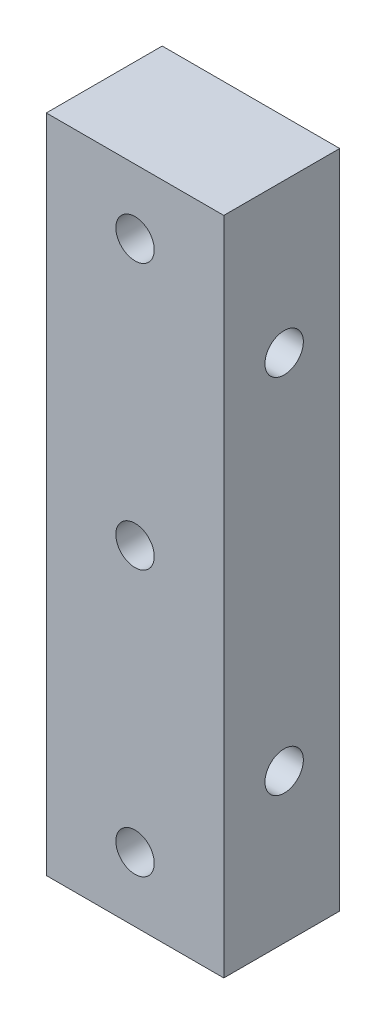
SolidWorks part; units mm, degrees
ref_plane "Front Plane" through (0, 0, 0) normal (0, 0, 1) x (1, 0, 0)
ref_plane "Top Plane" through (0, 0, 0) normal (0, 1, 0) x (1, 0, 0)
ref_plane "Right Plane" through (0, 0, 0) normal (1, 0, 0) x (0, 0, -1)
sketch "Sketch1" plane through (0, 0, 0) normal (0, 0, 1) x (1, 0, 0)
  line L1 (-9.3345, 34.7345) -> (9.3345, 34.7345)
  line L2 (-9.3345, 34.7345) -> (-9.3345, -34.7345)
  line L3 (-9.3345, -34.7345) -> (9.3345, -34.7345)
  line L4 (9.3345, 34.7345) -> (9.3345, -34.7345)
  line L5 (-9.3345, 34.7345) -> (9.3345, -34.7345) construction
  line L6 (-9.3345, -34.7345) -> (9.3345, 34.7345) construction
  point P0 (0, 0)
  dimension "D1" = 18.669
  dimension "D2" = 69.469
extrude "Boss-Extrude1" add sketch "Sketch1" along normal blind 12.192
sketch "Sketch2" plane through (9.3345, 0, 0) normal (1, 0, 0) x (0, 0, -1)
  line L0 (-5.842, 19.05) -> (-5.842, -19.05) construction
  line L1 (-12.192, -34.7345) -> (-12.192, 34.7345) construction
  line L2 (0, -34.7345) -> (0, 34.7345) construction
  point P2 (-5.842, 0)
  point P7 (0, 0)
  dimension "D1" = 6.35
  dimension "D2" = 38.1
hole_wizard "Tap Drill for #10-32 Tap1" positions "Sketch3" profile "Sketch4" hole size "#10-32" standard "ANSI Inch" end condition through all
sketch "Sketch3" plane through (9.3345, 0, 0) normal (1, 0, 0) x (0, 0, -1)
  point P0 (-5.842, 19.05)
  point P3 (-5.842, -19.05)
sketch "Sketch4" plane through (9.3345, 19.05, 5.842) normal (0, 1, 0) x (0, 0, -1)
  line L0 (0, 0) -> (0, 18.669)
  line L1 (0, 18.669) -> (2.0193, 18.669)
  line L2 (2.0193, 18.669) -> (2.0193, 0)
  line L5 (2.0193, 0) -> (0, 0)
  line L11 (0, -6.35) -> (0, 107.95) construction
  dimension "Thru Hole Dia." = 4.0386
  dimension "Thru Hole Depth" = 18.669
sketch "Sketch5" plane through (0, 0, 12.192) normal (0, 0, 1) x (1, 0, 0)
  line L0 (0, 27.94) -> (0, -27.94) construction
  point P3 (0, 0)
  dimension "D1" = 55.88
hole_wizard "Tap Drill for #10-32 Tap2" positions "Sketch6" profile "Sketch8" hole size "#10-32" standard "ANSI Inch" end condition through all
sketch "Sketch6" plane through (0, 0, 12.192) normal (0, 0, 1) x (1, 0, 0)
  point P0 (0, 27.94)
  point P3 (0, -27.94)
  point P7 (0, 0)
sketch "Sketch8" plane through (0, 27.94, 12.192) normal (1, 0, 0) x (0, -1, 0)
  line L0 (0, 0) -> (0, 12.192)
  line L1 (0, 12.192) -> (2.0193, 12.192)
  line L2 (2.0193, 12.192) -> (2.0193, 0)
  line L5 (2.0193, 0) -> (0, 0)
  line L11 (0, -6.35) -> (0, 107.95) construction
  dimension "Thru Hole Dia." = 4.0386
  dimension "Thru Hole Depth" = 12.192
sketch "Sketch9" plane through (0, -34.7345, 0) normal (0, -1, 0) x (1, 0, 0)
  line L0 (-9.3345, 12.192) -> (9.3345, 12.192) construction
  line L1 (-9.3345, 0) -> (9.3345, 0) construction
  point P0 (0, -6.858)
  point P4 (0, 0)
  dimension "D1" = 19.05
